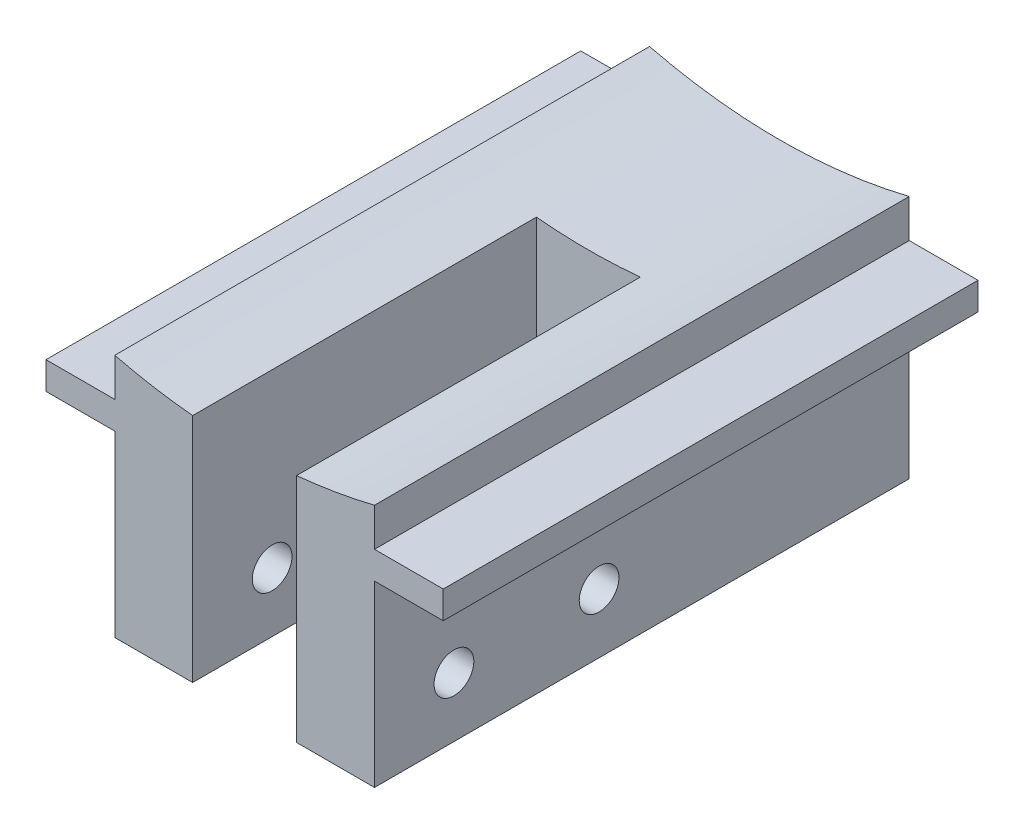
SolidWorks part; units mm, degrees
ref_plane "前基準面" through (0, 0, 0) normal (0, 0, 1) x (1, 0, 0)
ref_plane "上基準面" through (0, 0, 0) normal (0, 1, 0) x (1, 0, 0)
ref_plane "右基準面" through (0, 0, 0) normal (1, 0, 0) x (0, 0, -1)
ref_axis "基準軸1" through (0, -55, 0) along (0, 1, 0)
ref_axis "基準軸2" through (-88.99, 0, 0) along (1, 0, 0)
ref_axis "基準軸3" through (0, 0, 55) along (0, 0, -1)
sketch "草圖2" plane through (0, 0, 0) normal (0, 0, 1) x (1, 0, 0)
  line L1 (-8.5, -8) -> (8.5, -8)
  line L2 (-8.5, -8) -> (-8.5, 8)
  line L4 (8.5, -8) -> (8.5, 8)
  line L5 (9.35, 0) -> (-9.35, 0) construction
  line L6 (0, -55) -> (0, 55) construction
  arc A0 (-8.5, 8) -> (8.5, 8) centre (0, 42.4674) ccw
  point P7 (-8.5, 0)
  dimension "D3" = 71
  dimension "D4" = 8.5
  dimension "D1" = 16
  dimension "D2" = 17
extrude "填料-伸長1" add sketch "草圖2" against normal blind 35
sketch "草圖3" plane through (0, 0, 0) normal (0, 0, 1) x (1, 0, 0)
  line L0 (-8.5, -8) -> (8.5, -8) construction
  line L1 (-3.4, -8) -> (3.4, -8)
  line L2 (-3.4, -8) -> (-3.4, 7.1306)
  line L4 (3.4, -8) -> (3.4, 7.1306)
  line L5 (0, -8.8) -> (0, 8.8) construction
  arc A0 (-3.4, 7.1306) -> (3.4, 7.1306) centre (0, 42.4674) ccw
  arc A1 (-8.5, 8) -> (8.5, 8) centre (0, 42.4674) ccw construction
  point P6 (0, -8)
  dimension "D2" = 71
  dimension "D1" = 6.8
extrude "除料-伸長1" cut sketch "草圖3" against normal blind 22.5
sketch "草圖5" plane through (-8.5, 0, 0) normal (-1, 0, 0) x (0, 0, 1)
  line L0 (-35, -8) -> (0, -8) construction
  line L1 (0, -8.8) -> (0, 8.8) construction
  circle A0 centre (-5.2, -4.1) radius 1.3
  circle A1 centre (-14.7, -4.1) radius 1.3
  dimension "D1" = 2.6
  dimension "D2" = 2.6
  dimension "D3" = 3.9
  dimension "D4" = 5.2
  dimension "D5" = 9.5
extrude "除料-伸長3" cut sketch "草圖5" against normal through all
sketch "草圖6" plane through (0, 0, 0) normal (0, 0, 1) x (1, 0, 0)
  line L0 (8.5, -8) -> (8.5, 8) construction
  line L1 (8.5, 5.5) -> (13, 5.5)
  line L2 (8.5, 5.5) -> (8.5, 3.7)
  line L3 (8.5, 3.7) -> (13, 3.7)
  line L4 (13, 5.5) -> (13, 3.7)
  line L5 (0, -8.8) -> (0, 8.8) construction
  dimension "D1" = 2.5
  dimension "D2" = 1.8
  dimension "D3" = 13
extrude "填料-伸長2" add sketch "草圖6" against normal blind 35
mirror "鏡射1" about plane through (0, 0, 0) normal (1, 0, 0) of "填料-伸長2"
